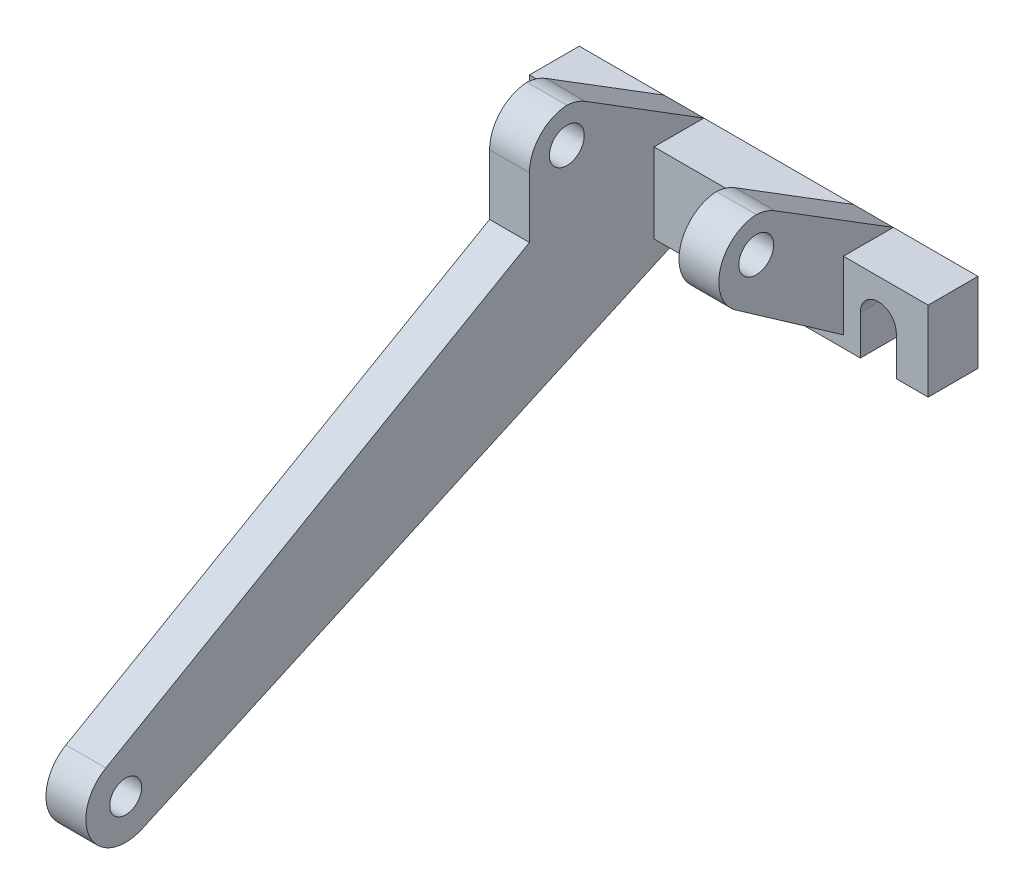
SolidWorks part; units mm, degrees
ref_plane "Front Plane" through (0, 0, 0) normal (0, 0, 1) x (1, 0, 0)
ref_plane "Top Plane" through (0, 0, 0) normal (0, 1, 0) x (1, 0, 0)
ref_plane "Right Plane" through (0, 0, 0) normal (1, 0, 0) x (0, 0, -1)
sketch "Sketch1" plane through (0, 0, 0) normal (0, 0, 1) x (1, 0, 0)
  line L0 (15, 0) -> (-15, 0) construction
  line L1 (-20, 4) -> (20, 4)
  line L2 (-20, 4) -> (-20, -4)
  line L3 (-20, -4) -> (-16.8, -4)
  line L4 (20, 4) -> (20, -4)
  line L5 (-20, 4) -> (20, -4) construction
  line L6 (-20, -4) -> (20, 4) construction
  line L7 (0, -4) -> (0, 4) construction
  line L8 (-16.8, 0) -> (-16.8, -4)
  line L9 (13.2, -4) -> (13.2, 0)
  line L10 (-13.2, -4) -> (-13.2, 0)
  line L11 (-13.2, -4) -> (13.2, -4)
  line L12 (16.8, 0) -> (16.8, -4)
  line L13 (16.8, -4) -> (20, -4)
  arc A0 (-13.2, 0) -> (-16.8, 0) centre (-15, 0) ccw
  arc A1 (13.2, 0) -> (16.8, 0) centre (15, 0) cw
  point P0 (0, 0)
  point P12 (0, 0)
  dimension "D3" = 3.6
  dimension "D1" = 40
  dimension "D2" = 8
  dimension "D4" = 15
extrude "Boss-Extrude1" add sketch "Sketch1" along normal blind 5
sketch "Sketch2" plane through (0, 0, 5) normal (0, 0, 1) x (1, 0, 0)
  line L0 (0, 4) -> (0, -4) construction
  line L1 (20, 4) -> (-20, 4) construction
  line L2 (-20, -4) -> (-16.8, -4) construction
  line L3 (11.5, -4) -> (7.5, 4) construction
  line L4 (-11.5, 4) -> (-7.5, 4)
  line L5 (-11.5, 4) -> (-11.5, -4)
  line L6 (-11.5, -4) -> (-7.5, -4)
  line L7 (-7.5, 4) -> (-7.5, -4)
  line L8 (-11.5, 4) -> (-7.5, -4) construction
  line L9 (-11.5, -4) -> (-7.5, 4) construction
  line L10 (11.5, 4) -> (7.5, -4) construction
  line L11 (7.5, 4) -> (7.5, -4)
  line L12 (11.5, -4) -> (7.5, -4)
  line L13 (11.5, 4) -> (11.5, -4)
  line L14 (11.5, 4) -> (7.5, 4)
  line L16 (-13.2, -4) -> (13.2, -4) construction
  point P6 (-9.5, 0)
  point P15 (9.5, 0)
  dimension "D1" = 7.5
  dimension "D2" = 4
extrude "Boss-Extrude2" add sketch "Sketch2" along normal blind 12.5
sketch "Sketch4" plane through (0, 4, 0) normal (0, 1, 0) x (1, 0, 0)
  line L0 (-7.5, -17.5) -> (-7.5, -5) construction
  line L1 (-11.5, -17.5) -> (-7.5, -17.5)
  line L2 (-11.5, -17.5) -> (-11.5, -10)
  line L3 (-11.5, -10) -> (-7.5, -10)
  line L4 (-7.5, -17.5) -> (-7.5, -10)
  line L5 (0, 0) -> (0, -5) construction
  line L6 (7.5, -5) -> (-7.5, -5) construction
  line L7 (7.5, -17.5) -> (7.5, -10)
  line L8 (11.5, -10) -> (7.5, -10)
  line L9 (11.5, -17.5) -> (11.5, -10)
  line L10 (11.5, -17.5) -> (7.5, -17.5)
  dimension "D1" = 7.5
extrude "Boss-Extrude3" add sketch "Sketch4" along normal blind 8
sketch "Sketch3" plane through (-11.5, 0, 0) normal (-1, 0, 0) x (0, 0, 1)
  line L0 (10, 8.5) -> (17.5, 8.5) construction
  line L4 (10, 12) -> (10, 4) construction
  line L5 (17.5, 12) -> (17.5, -4) construction
  line L6 (13.75, 8.5) -> (13.75, 12) construction
  line L7 (10, 12) -> (17.5, 12) construction
  circle A0 centre (13.75, 8.5) radius 1.75
  dimension "D1" = 3.5
  dimension "D2" = 8.5
extrude "Cut-Extrude1" cut sketch "Sketch3" against normal through all
fillet "Fillet1" radius 4 4 edges at (-9.5, 12, 10) (9.5, 12, 10) (9.5, 12, 17.5) (-9.5, 12, 17.5)
sketch "Sketch5" plane through (-7.5, 0, 0) normal (1, 0, 0) x (0, 0, -1)
  line L0 (-10, 8) -> (-10, 4) construction
  line L1 (-10, 6.5) -> (-13, 6.5)
  line L2 (-10, 6.5) -> (-10, 1.5)
  line L3 (-10, 1.5) -> (-13, 1.5)
  line L4 (-13, 6.5) -> (-13, 1.5)
  line L5 (-10, 4) -> (-5, 4) construction
  dimension "D1" = 3
  dimension "D2" = 5
  dimension "D3" = 2.5
extrude "Boss-Extrude4" [suppressed] add sketch "Sketch5" along normal up to next
sketch "Sketch6" plane through (-11.5, 0, 0) normal (-1, 0, 0) x (0, 0, 1)
  line L0 (56.0113, -29.4012) -> (11.7824, -4)
  line L1 (17.5, -4) -> (5, -4) construction
  line L2 (11.7824, -4) -> (17.5, 1.9418)
  line L3 (13.75, 8.5) -> (58.0033, -25.9326) construction
  line L4 (17.5, 1.9418) -> (59.9954, -22.4639)
  line L5 (59.9954, -22.4639) -> (56.0113, -29.4012) construction
  line L6 (13.75, 8.5) -> (13.75, -4) construction
  line L7 (17.5, 8) -> (17.5, -4) construction
  circle A0 centre (58.0033, -25.9326) radius 1.6
  arc A1 (56.0113, -29.4012) -> (59.9954, -22.4639) centre (58.0033, -25.9326) ccw
  dimension "D1" = 3.2
  dimension "D2" = 8
  dimension "D3" = 52.114
  dimension "D4" = 56.071
  dimension "D5" = 1.9676
extrude "Boss-Extrude5" add sketch "Sketch6" against normal up to surface (4 mm away) up to face at (-7.5, 6.75, 13.75)
sketch "Sketch7" plane through (-11.5, 0, 0) normal (-1, 0, 0) x (0, 0, 1)
  line L0 (1.4608, 4) -> (11.0845, 10.7386)
  line L1 (5, 4) -> (0, 4) construction
  line L2 (11.0845, 10.7386) -> (10, 4)
  line L3 (10, 8) -> (10, 4) construction
  line L4 (10, 4) -> (1.4608, 4)
  arc A0 (13.75, 11.9922) -> (10, 8) centre (14, 8) ccw construction
  dimension "D1" = 35
extrude "Boss-Extrude6" add sketch "Sketch7" against normal up to surface (4 mm away) up to face at (-7.5, -2.4438, 21.5899)
sketch "Sketch8" plane through (11.5, 0, 0) normal (1, 0, 0) x (0, 0, -1)
  line L0 (-1.4608, 4) -> (-11.0845, 10.7386)
  line L1 (-11.0845, 10.7386) -> (-10, 4)
  line L2 (-10, 4) -> (-1.4608, 4)
  arc A0 (-10, 8) -> (-13.75, 11.9922) centre (-14, 8) ccw construction
extrude "Boss-Extrude7" add sketch "Sketch8" against normal up to surface (4 mm away) up to face at (7.5, 10.25, 13.75)
sketch "Sketch9" plane through (11.5, 0, 0) normal (1, 0, 0) x (0, 0, -1)
  line L0 (-15.7943, 4.7234) -> (-5, -2.8349)
  line L1 (-5, -4) -> (-5, 4) construction
  line L2 (-5, -2.8349) -> (-5, -4)
  line L3 (-5, -4) -> (-17.5, -4)
  line L4 (-17.5, -4) -> (-17.5, 8) construction
  line L5 (-17.5, -4) -> (-5, -4) construction
  line L6 (-17.5, -4) -> (-17.5, 8)
  line L7 (-1.4608, 4) -> (-11.0845, 10.7386) construction
  arc A0 (-17.5, 8) -> (-15.7943, 4.7234) centre (-13.5, 8) ccw
  arc A1 (-13.75, 11.9922) -> (-17.5, 8) centre (-13.5, 8) ccw construction
extrude "Cut-Extrude2" cut sketch "Sketch9" against normal up to next
sketch "Sketch10" plane through (11.5, 0, 0) normal (1, 0, 0) x (0, 0, -1)
  line L0 (0, 4) -> (-11.8868, 11.3962)
  line L1 (-11.8868, 11.3962) -> (-5, 4)
  line L2 (-5, 4) -> (0, 4)
  arc A0 (-11.0845, 10.7386) -> (-13.75, 11.9922) centre (-14, 8) ccw construction
extrude "Boss-Extrude8" add sketch "Sketch10" against normal blind 4
ref_plane "Plane1" through (0, 0, 0) normal (-1, 0, 0) x (0, 0, 1)
mirror "Mirror1" about plane through (0, 0, 0) normal (-1, 0, 0) of "Boss-Extrude8"
sketch "Sketch11" plane through (-7.5, 0, 0) normal (1, 0, 0) x (0, 0, -1)
  line L0 (0, -4) -> (-56.3502, -29.575)
  line L1 (-56.3502, -29.575) -> (-11.7824, -4)
  line L2 (-11.7824, -4) -> (0, -4)
  line L3 (0, -4) -> (-0.1024, -3.7913)
  arc A0 (-59.9954, -22.4639) -> (-56.0113, -29.4012) centre (-58.0033, -25.9326) ccw construction
  arc M7 (-59.9954, -22.4639) -> (-56.0113, -29.4012) centre (-58.0033, -25.9326) ccw
  line M8 (-56.0113, -29.4012) -> (-11.7824, -4)
  line M9 (-11.7824, -4) -> (-5, -4)
extrude "Boss-Extrude9" add sketch "Sketch11" against normal up to surface (4 mm away) contours L2 L0 M9 M8 M7 region at (-7.5, -12.4988, 22.6531) up to face at (-11.5, -1.5669, 20.3539)
equation "\"X-ROD-SPACING\"=45"
equation "\"Y-ROD-SPACING\"=75"
equation "\"Z-ROD-SPACING\"=17.5"
equation "\"Y-BED-OFFSET\"=2"
equation "\"Y-BED-ROD-INSET\"=3.5"
equation "\"Y-BED-SCREW-SPACING\"=209"
equation "\"Y-BED-SCREW-CUTOUT-SLOT-HEIGHT\"=2.5"
equation "\"T-SLOT-NUT-FILLET-RADIUS\"=0.5"
equation "\"T-SLOT-SCREW-SHAFT-RADIUS\"=1.55"
equation "\"T-SLOT-SCREW-SHAFT-CUTOUT-LENGTH\"=11"
equation "\"T-SLOT-NUT-DEPTH\"=3.5"
equation "\"T-SLOT-NUT-WIDTH\"=2.85"
equation "\"T-SLOT-NUT-END-DISTANCE\"=8"
equation "\"ACRYLIC-THICKNESS\"=10"
equation "\"ACRYLIC-THICKNESS2\"=4.5"
equation "\"ACRYLIC-TAB-CUTOUT-SIZE\"=\"ACRYLIC-THICKNESS\"+\"ACRYLIC-TAB-TOLERANCE\"*2"
equation "\"ACRYLIC-TAB-TOLERANCE\"=-.05"
equation "\"ACRYLIC-TAB-WIDTH\"=\"ACRYLIC-THICKNESS\""
equation "\"ACRYLIC-M3-HOLE\"=2.9"
equation "\"SMOOTHROD-CAP-SCREW-DISTANCE\"=20"
equation "\"FRAME-WIDTH-INNER\"=370"
equation "\"NEMA17-HOLE-SPACING\"=31"
equation "\"NEMA17-CENTRAL-CUTOUT\"=22.5"
equation "\"Z-BRACKET-REACH\"=57"
equation "\"Z-ROD-INSET\"=13.5"
equation "\"TOP-BRACKET-SPACING\"=40"
equation "\"SMOOTHROD-X-LENGTH\"=350"
equation "\"SMOOTHROD-Y-LENGTH\"=350"
equation "\"SMOOTHROD-Z-LENGTH\"=350"
equation "\"SMOOTHROD-TIGHTENING-HEADROOM\"=.25"
equation "\"LEADSCREW-Z-LENGTH\"=300"
equation "\"SCREW-LENGTH-FRAME\"=\"ACRYLIC-THICKNESS\" + 10"
equation "\"SCREW-LENGTH-MOTOR\"=\"ACRYLIC-THICKNESS\" + 5"
equation "\"SCREW-LENGTH-EXTRUDER\"=28"
equation "\"SCREW-HEAD-RADIUS\"=6"
equation "\"PRINTED-X-SMOOTHROD-DIAMETER\"=8.8"
equation "\"PRINTED-X-SMOOTHROD-CUTOUT\"=10"
equation "\"PRINTED-X-BASE-HEIGHT\"=10"
equation "\"PRINTED-LM8UU-CUTOUT-SIZE\"=15.5"
equation "\"PRINTED-LM8UU-CUTOUT-LENGTH\"=24.5"
equation "\"PRINTED-X-IDLER-HEIGHT\"=16"
equation "\"PSU-MOUNTING-WIDTH\"=50"
equation "\"PSU-MOUNTING-HEIGHT\"=150"
equation "\"Y-BELT-TO-ROD-DISTANCE\"=20"
equation "\"SPOOL-HOLDER-ROD-SPACING\"=150"
equation "\"ACRYLIC-X-CARRIAGE-WIDTH\"=55"
equation "\"ACRYLIC-X-CARRIAGE-HEIGHT\"=75"
equation "\"ACRYLIC-X-CARRIAGE-LM8UU-CUTOUT-WIDTH\"=24.25"
equation "\"ACRYLIC-X-CARRIAGE-LM8UU-CUTOUT-HEIGHT\"=11.0"
equation "\"ACRYLIC-X-CARRIAGE-SCREW-SPACING-X\"=15"
equation "\"ACRYLIC-X-CARRIAGE-SCREW-SPACING-Y\"=33"
equation "\"ACRYLIC-X-CARRIAGE-CENTER-TAB-SPACING\"=14"
equation "\"ACRYLIC-X-CARRIAGE-EXTRUDER-OFFSET\"=26"
equation "\"ACRYLIC-X-CARRIAGE-EXTRUDER-ANGLE\"=90"
equation "\"ACRYLIC-X-CARRIAGE-EXTRUDER-SHELF-DEPTH\"=\"ACRYLIC-X-CARRIAGE-EXTRUDER-OFFSET\" + 28"
equation "\"ACRYLIC-X-CARRIAGE-EXTRUDER-BRACE-SPACING\"=23"
equation "\"ACRYLIC-X-CARRIAGE-EXTRUDER-BRACE-TAB-OFFSET\"=20"
equation "\"ACRYLIC-X-CARRIAGE-EXTRUDER-BRACE-HEIGHT\"=35"
equation "\"ACRYLIC-X-CARRIAGE-EXTRUDER-BRACE-SCREW-SPACING\"=22"
equation "\"ACRYLIC-X-CARRIAGE-DUAL-WIDTH-MULTIPLIER\"=1.65"
equation "\"ACRYLIC-X-CARRIAGE-DUAL-HOTEND-SPACING\"=42"
equation "\"ACRYLIC-X-CARRIAGE-DUAL-WIDTH\"=75"
equation "\"ACRYLIC-X-CARRIAGE-DUAL-HOTEND-SEPARATION\"=36"
equation "\"ACRYLIC-X-CARRIAGE-DUAL-MOUNT-PLATE-DEPTH\"=75"
equation "\"ACRYLIC-X-CARRIAGE-DUAL-MOUNT-BRACE-WIDTH\"=33"
equation "\"ACRYLIC-X-CARRIAGE-DUAL-MOUNT-SCREW-WIDTH\"=40"
equation "\"D3@Sketch1\"=3.6"
equation "\"PRINTED-M3-HOLE\"=3.5"
equation "\"BLOWER-FAN-WIDTH\"=15"
equation "\"D1@Sketch2\"=\"BLOWER-FAN-WIDTH\"/2"
